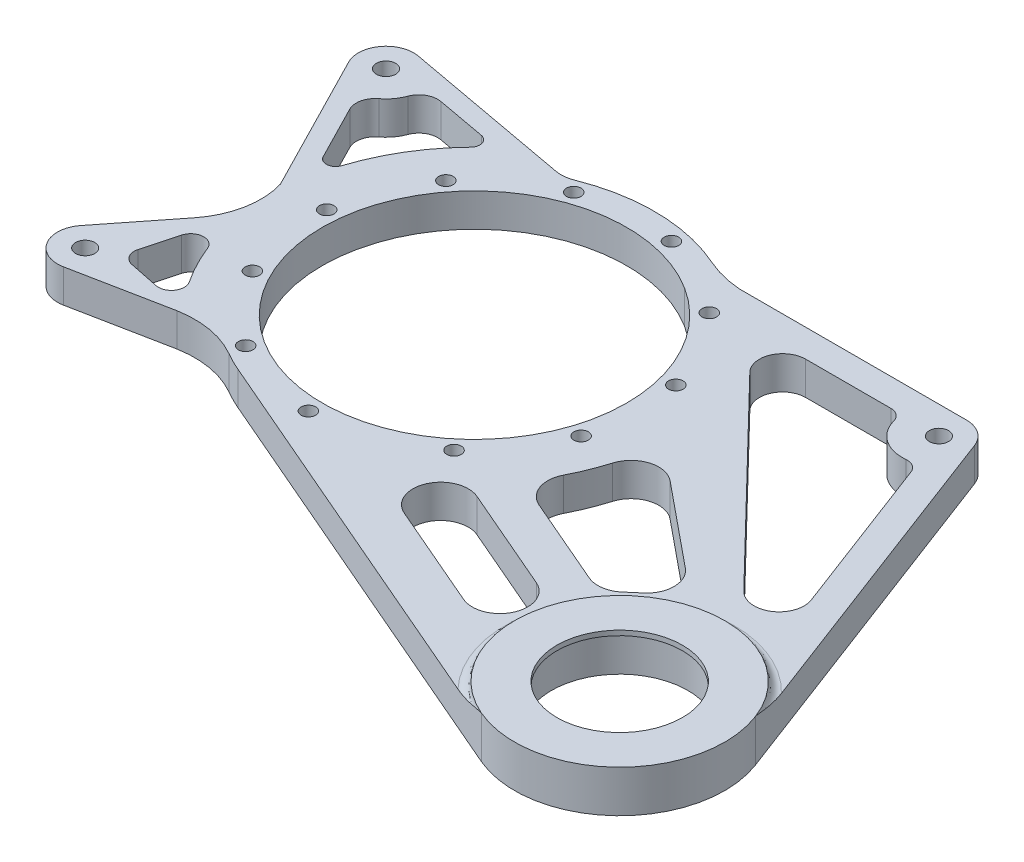
SolidWorks part; units mm, degrees
material "7075-T6 (SN)"
ref_plane "X-Y Datum" through (0, 0, 0) normal (0, 0, 1) x (1, 0, 0)
ref_plane "X-Z Datum" through (0, 0, 0) normal (0, 1, 0) x (1, 0, 0)
ref_plane "Y-Z Datum" through (0, 0, 0) normal (1, 0, 0) x (0, 0, -1)
sketch "Sketch1" plane through (0, 0, 0) normal (0, 1, 0) x (1, 0, 0)
  line L0 (-452.4939, -193.2569) -> (-599.8423, -129.6662)
  line L3 (-568.96, 0) -> (-463.042, 0) construction
  line L4 (-685.8, 0) -> (-568.96, 0) construction
  line L5 (-685.8, -143.2733) -> (-685.8, 0) construction
  line L6 (-685.8, -143.2733) -> (-575.31, -72.8215) construction
  line L7 (-575.31, -72.8215) -> (-438.15, -160.02) construction
  line L8 (-685.8, -1.6598) -> (-575.31, -72.8215) construction
  line L9 (-537.4328, -19.4168) -> (-459.3604, -19.4168)
  line L14 (-652.4813, -91.9261) -> (-669.8039, -113.9002)
  line L15 (-673.1, -130.5733) -> (-698.5, -130.5733) construction
  line L16 (-673.1, -130.5733) -> (-673.1, -155.9733) construction
  line L17 (-673.1, -155.9733) -> (-698.5, -155.9733) construction
  line L18 (-698.5, -130.5733) -> (-698.5, -155.9733) construction
  line L19 (-673.1, -130.5733) -> (-698.5, -155.9733) construction
  line L20 (-673.1, -155.9733) -> (-698.5, -130.5733) construction
  line L21 (-627.8464, -122.6884) -> (-660.4758, -129.1411)
  line L22 (-662.2354, -5.2529) -> (-604.1922, -15.9133)
  line L23 (-672.4346, -18.9616) -> (-647.7651, -67.1526)
  line L25 (-673.1, -12.7) -> (-698.5, -12.7) construction
  line L26 (-673.1, -12.7) -> (-673.1, 12.7) construction
  line L27 (-673.1, 12.7) -> (-698.5, 12.7) construction
  line L28 (-698.5, -12.7) -> (-698.5, 12.7) construction
  line L29 (-673.1, -12.7) -> (-698.5, 12.7) construction
  line L30 (-673.1, 12.7) -> (-698.5, -12.7) construction
  line L32 (-685.8, -130.5733) -> (-673.1, -130.5733) construction
  line L33 (-685.8, -129.1488) -> (-685.8, -130.5733) construction
  line L34 (-668.5282, -112.57) -> (-684.4718, -126.258) construction
  line L35 (-667.4361, -138.3507) -> (-655.5968, -126.5405) construction
  line L36 (-673.1, -139.4633) -> (-670.1269, -139.4633) construction
  line L37 (-673.1, -130.5733) -> (-673.1, -139.4633) construction
  line L38 (-685.8, -130.5733) -> (-673.1, -130.5733) construction
  line L39 (-685.8, -129.1488) -> (-685.8, -130.5733) construction
  line L40 (-668.5282, -112.57) -> (-684.4718, -126.258) construction
  line L41 (-667.4361, -138.3507) -> (-655.5968, -126.5405) construction
  line L42 (-673.1, -139.4633) -> (-670.1269, -139.4633) construction
  line L43 (-673.1, -130.5733) -> (-673.1, -139.4633) construction
  line L44 (-463.042, 0) -> (-463.042, -3.81) construction
  line L45 (-575.31, -72.8215) -> (-459.3604, -28.9418) construction
  line L46 (-450.455, -25.5624) -> (-404.305, -147.1765)
  line L47 (-575.31, -72.8215) -> (-575.31, -78.4445) construction
  line L48 (-655.8976, -11.4734) -> (-668.4375, -1.9195)
  line L49 (-670.3617, -1.27) -> (-673.1, -1.27)
  line L50 (-673.1, -1.27) -> (-673.1, -12.7)
  line L51 (-673.1, -12.7) -> (-684.53, -12.7)
  line L52 (-684.53, -12.7) -> (-684.53, -14.7065)
  line L53 (-682.9809, -17.4336) -> (-666.5478, -27.2313)
  line L56 (-673.1, -1.27) -> (-673.1, -12.7) construction
  line L57 (-673.1, -12.7) -> (-684.53, -12.7) construction
  circle A13 centre (-438.15, -160.02) radius 23.5
  circle A17 centre (-575.31, -72.8215) radius 61.9125 construction
  circle A18 centre (-575.31, -72.8215) radius 52.3875
  circle A29 centre (-438.15, -160.02) radius 36.2 construction
  arc A36 (-588.7133, -12.3772) -> (-550.1347, -16.2586) centre (-575.31, -72.8215) cw
  arc A38 (-627.8464, -122.6884) -> (-606.238, -126.4556) centre (-622.1949, -154.1272) cw
  circle A39 centre (-662.3237, -119.797) radius 3.3
  arc A45 (-684.4718, -126.258) -> (-685.8, -129.1488) centre (-681.99, -129.1488) ccw construction
  circle A46 centre (-662.3237, -119.797) radius 3.3
  circle A47 centre (-662.3237, -119.797) radius 3.3 construction
  arc A48 (-655.5968, -126.5405) -> (-668.5282, -112.57) centre (-662.3237, -119.797) ccw construction
  arc A49 (-670.1269, -139.4633) -> (-667.4361, -138.3507) centre (-670.1269, -135.6533) ccw construction
  arc A50 (-684.4718, -126.258) -> (-685.8, -129.1488) centre (-681.99, -129.1488) ccw construction
  arc A51 (-655.5968, -126.5405) -> (-668.5282, -112.57) centre (-662.3237, -119.797) ccw construction
  arc A52 (-670.1269, -139.4633) -> (-667.4361, -138.3507) centre (-670.1269, -135.6533) ccw construction
  circle A53 centre (-662.3237, -119.797) radius 9.525 construction
  arc A54 (-599.8423, -129.6662) -> (-606.238, -126.4556) centre (-575.31, -72.8215) cw
  arc A55 (-669.8039, -113.9002) -> (-660.4758, -129.1411) centre (-662.3237, -119.797) ccw
  circle A57 centre (-602.253, -5.3549) radius 10.7351 construction
  arc A58 (-588.7133, -12.3772) -> (-598.2717, -15.3244) centre (-575.31, -72.8215) ccw
  arc A59 (-668.4375, -1.9195) -> (-670.3617, -1.27) centre (-670.3617, -4.445) ccw
  arc A60 (-684.53, -14.7065) -> (-682.9809, -17.4336) centre (-681.355, -14.7065) ccw
  arc A61 (-666.5478, -27.2313) -> (-655.8976, -11.4734) centre (-661.67, -19.05) ccw
  arc A65 (-647.7651, -67.1526) -> (-652.4813, -91.9261) centre (-673.9475, -75.0039) cw
  arc A67 (-598.2717, -15.3244) -> (-604.1922, -15.9133) centre (-602.253, -5.3549) cw
  circle A68 centre (-463.042, -3.81) radius 12.7 construction
  circle A69 centre (-459.3604, -28.9418) radius 3.3
  circle A70 centre (-459.3604, -28.9418) radius 9.525 construction
  arc A71 (-550.1347, -16.2586) -> (-537.4328, -19.4168) centre (-534.8559, 18.0692) ccw
  arc A72 (-459.3604, -19.4168) -> (-450.455, -25.5624) centre (-459.3604, -28.9418) cw
  arc A73 (-452.4939, -193.2569) -> (-404.305, -147.1765) centre (-438.15, -160.02) ccw
  circle A74 centre (-685.8, -1.6598) radius 12.7 construction
  circle A75 centre (-663.956, -14.6213) radius 3.3
  circle A76 centre (-663.956, -14.6213) radius 9.525 construction
  arc A77 (-662.2354, -5.2529) -> (-672.4346, -18.9616) centre (-663.956, -14.6213) ccw
  dimension "D7" = 25.4
  dimension "D10" = 123.825
  dimension "D11" = 104.775
  dimension "D12" = 47
  dimension "D13" = 72.4
  dimension "D15" = 26.943
  dimension "D18" = 43.8797
  dimension "D24" = 31.9428
  dimension "D25" = 32.6295
  dimension "D26" = 9.344
  dimension "D29" = 21.9741
  dimension "D33" = 27.3342
  dimension "D34" = 21.844
  dimension "D23" = 19.05
  dimension "D32" = 25.4
  dimension "D38" = 3.81
  dimension "D28" = 21.4701
  dimension "D19" = 37.5744
  dimension "D17" = 25.4
  dimension "D22" = 19.05
  dimension "D1" = 685.8
  dimension "D2" = 116.84
  dimension "D3" = 222.758
  dimension "D5" = 160.02
  dimension "D6" = 117.8733
  dimension "D8" = 72.8215
  dimension "D9" = 110.49
  dimension "D14" = 25.4
  dimension "D16" = 25.1753
  dimension "D20" = 1.6598
  dimension "D21" = 25.4
  dimension "D27" = 247.65
  dimension "D30" = 7.4802
  dimension "D31" = 0
  dimension "D36" = 3.8814
  dimension "D37" = 25.4
  dimension "D43" = 0
extrude "Boss-Extrude1" add sketch "Sketch1" along normal mid plane 11.43
sketch "Sketch2" plane through (0, 5.715, 0) normal (0, 1, 0) x (1, 0, 0)
  circle A1 centre (-438.15, -160.02) radius 23.5 construction
  circle A2 centre (-438.15, -160.02) radius 36.2
  circle A3 centre (-438.15, -160.02) radius 36.2
  circle A4 centre (-438.15, -160.02) radius 23.5
  circle A5 centre (-438.15, -160.02) radius 21.595
  circle M23 centre (-438.15, -160.02) radius 23.5
  dimension "D1" = 12.7
  dimension "D2" = 1.905
extrude "Boss-Extrude2" add sketch "Sketch2" along normal blind 3.0464 contours A3 M23 | A5 M23 region at (-473.3261, 5.715, 160.02) region at (-460.9853, 5.715, 160.02)
fillet "Fillet1" radius 3.175 1 edges at (-463.1685, 5.715, 133.8567)
sketch "Sketch6" plane through (0, 5.715, 0) normal (0, -1, 0) x (1, 0, 0)
  circle A0 centre (-438.15, 160.02) radius 23.5 construction
  circle A1 centre (-438.15, 160.02) radius 21.595
  circle A2 centre (-438.15, 160.02) radius 21.595
  circle A3 centre (-438.15, 160.02) radius 23.5
  dimension "D1" = 0
extrude "Cut-Extrude1" cut sketch "Sketch6" against normal blind 1.392
ref_point "Point1"
ref_point "Point2"
ref_plane "Plane1" through (-438.15, 0.696, 160.02) normal (0.8439, 0, 0.5365) x (0.5365, 0, -0.8439)
ref_plane "Plane2" through (-376.7454, 0, -239.5133) normal (0.8439, 0, 0.5365) x (0.5365, 0, -0.8439)
split line "Split Line1"
split line "Split Line2"
sketch "Sketch8" plane through (0, -5.715, 0) normal (0, -1, 0) x (1, 0, 0)
  circle A0 centre (-575.31, 72.8215) radius 61.9125 construction
  circle A1 centre (-575.31, 72.8215) radius 61.9125
split line "Split Line5"
sketch "Sketch11" plane through (0, -5.715, 0) normal (0, -1, 0) x (1, 0, 0)
  line L0 (-432.5061, 99.7078) -> (-453.4854, 44.4233)
  line L1 (-505.1999, 28.9418) -> (-475.9191, 28.9418)
  line L2 (-446.7225, 108.7412) -> (-510.9243, 42.4554)
  line L6 (-459.3604, 19.4168) -> (-537.4328, 19.4168) construction
  line L8 (-520.863, 126.4041) -> (-484.9521, 141.902)
  line L9 (-507.6372, 118.2797) -> (-477.2622, 131.3885)
  line L10 (-492.3338, 88.4923) -> (-463.6028, 111.9632)
  line L19 (-658.1742, 32.8834) -> (-648.5837, 51.6181)
  line L20 (-644.8026, 14.9109) -> (-627.7247, 18.0475)
  line L21 (-672.4346, 18.9616) -> (-647.7651, 67.1526) construction
  line L22 (-662.2354, 5.2529) -> (-604.1922, 15.9133) construction
  line L23 (-672.4346, 18.9616) -> (-647.7651, 67.1526) construction
  line L24 (-662.2354, 5.2529) -> (-604.1922, 15.9133) construction
  line L25 (-662.3237, 119.797) -> (-575.31, 72.8215) construction
  line L26 (-652.7583, 111.1604) -> (-649.5762, 99.3396)
  line L27 (-649.3552, 116.671) -> (-638.88, 118.8094)
  line L28 (-528.4114, 143.8948) -> (-492.5005, 159.3927)
  line L29 (-599.8423, 129.6662) -> (-452.4939, 193.2569) construction
  line L30 (-404.305, 147.1765) -> (-450.455, 25.5624) construction
  circle A0 centre (-440.5457, 102.7586) radius 8.599 construction
  circle A1 centre (-505.1999, 36.911) radius 7.9692 construction
  circle A2 centre (-475.9191, 33.3868) radius 4.445 construction
  circle A3 centre (-457.6413, 46.0004) radius 4.445 construction
  arc A4 (-475.9191, 28.9418) -> (-471.6261, 32.2344) centre (-475.9191, 33.3868) ccw
  circle A6 centre (-575.31, 72.8215) radius 70.8025
  circle A7 centre (-575.31, 72.8215) radius 70.8025 construction
  circle A9 centre (-459.3604, 28.9418) radius 12.7 construction
  arc A10 (-471.6261, 32.2344) -> (-458.087, 41.5778) centre (-459.3604, 28.9418) cw
  arc A11 (-453.4854, 44.4233) -> (-458.087, 41.5778) centre (-457.6413, 46.0004) cw
  arc A12 (-432.5061, 99.7078) -> (-446.7225, 108.7412) centre (-440.5457, 102.7586) ccw
  arc A13 (-505.1999, 28.9418) -> (-510.9243, 42.4554) centre (-505.1999, 36.911) cw
  circle A14 centre (-524.6372, 135.1494) radius 9.525 construction
  circle A15 centre (-488.7263, 150.6474) radius 9.525 construction
  circle A16 centre (-503.863, 109.5343) radius 9.525 construction
  circle A17 centre (-473.488, 122.6432) radius 9.525 construction
  arc A19 (-512.335, 105.181) -> (-507.4844, 93.1359) centre (-575.31, 72.8215) cw
  circle A20 centre (-498.3598, 95.8688) radius 9.525 construction
  arc A23 (-528.4114, 143.8948) -> (-520.863, 126.4041) centre (-524.6372, 135.1494) ccw
  arc A24 (-492.5005, 159.3927) -> (-484.9521, 141.902) centre (-488.7263, 150.6474) cw
  arc A25 (-507.6372, 118.2797) -> (-512.335, 105.181) centre (-503.863, 109.5343) ccw
  arc A26 (-507.4844, 93.1359) -> (-492.3338, 88.4923) centre (-498.3598, 95.8688) ccw
  circle A28 centre (-469.6288, 119.3397) radius 9.525 construction
  arc A29 (-466.9443, 129.5645) -> (-463.7997, 126.8727) centre (-438.15, 160.02) ccw
  arc A30 (-477.2622, 131.3885) -> (-466.9443, 129.5645) centre (-473.488, 122.6432) cw
  arc A31 (-463.7997, 126.8727) -> (-463.6028, 111.9632) centre (-469.6288, 119.3397) cw
  arc A34 (-468.5527, 188.87) -> (-407.9695, 130.9376) centre (-438.15, 160.02) ccw
  arc A35 (-468.5527, 188.87) -> (-407.9695, 130.9376) centre (-438.15, 160.02) ccw construction
  circle A52 centre (-652.4088, 29.932) radius 6.477 construction
  circle A53 centre (-645.9727, 21.2814) radius 6.477 construction
  circle A54 centre (-645.7462, 50.1656) radius 3.1877 construction
  circle A55 centre (-628.3005, 21.1828) radius 3.1877 construction
  arc A57 (-642.7116, 51.1417) -> (-626.0175, 23.4075) centre (-575.31, 72.8215) ccw
  arc A60 (-642.7116, 51.1417) -> (-648.5837, 51.6181) centre (-645.7462, 50.1656) ccw
  arc A61 (-626.0175, 23.4075) -> (-627.7247, 18.0475) centre (-628.3005, 21.1828) cw
  circle A63 centre (-648.4662, 112.3158) radius 4.445 construction
  circle A64 centre (-637.9909, 114.4542) radius 4.445 construction
  circle A65 centre (-645.284, 100.4951) radius 4.445 construction
  arc A66 (-641.1505, 98.8604) -> (-634.2883, 111.9949) centre (-575.31, 72.8215) cw
  arc A67 (-652.7583, 111.1604) -> (-649.3552, 116.671) centre (-648.4662, 112.3158) cw
  arc A68 (-638.88, 118.8094) -> (-634.2883, 111.9949) centre (-637.9909, 114.4542) cw
  arc A69 (-641.1505, 98.8604) -> (-649.5762, 99.3396) centre (-645.284, 100.4951) cw
  circle A70 centre (-459.3604, 28.9418) radius 3.3 construction
  circle A71 centre (-459.3604, 28.9418) radius 3.3 construction
  arc A74 (-656.3088, 24.7608) -> (-652.0465, 19.0319) centre (-663.956, 14.6213) cw
  circle A75 centre (-663.956, 14.6213) radius 12.7
  circle A76 centre (-663.956, 14.6213) radius 12.7 construction
  arc A77 (-658.1742, 32.8834) -> (-656.3088, 24.7608) centre (-652.4088, 29.932) ccw
  arc A78 (-652.0465, 19.0319) -> (-644.8026, 14.9109) centre (-645.9727, 21.2814) ccw
  dimension "D3" = 8.89
  dimension "D6" = 25.4
  dimension "D10" = 19.05
  dimension "D15" = 12.954
  dimension "D16" = 6.3754
  dimension "D19" = 8.89
  dimension "D4" = 9.525
  dimension "D5" = 9.525
  dimension "D7" = 73.8169
  dimension "D8" = 29.0831
  dimension "D9" = 15.24
  dimension "D11" = 12.7
  dimension "D12" = 14.732
  dimension "D14" = 5.08
  dimension "D17" = 6.35
  dimension "D18" = 6.35
  dimension "D20" = 8.89
  dimension "D21" = 6.858
  dimension "D22" = 15.748
  dimension "D23" = 45.8396
  dimension "D1" = 8.89
  dimension "D13" = 2.54
  dimension "D24" = 3.175
extrude "Cut-Extrude3" cut sketch "Sketch11" against normal through all
sketch "Sketch12" plane through (0, -5.715, 0) normal (0, -1, 0) x (1, 0, 0)
  line L0 (-575.31, 72.8215) -> (-575.31, 159.4351) construction
  line L1 (-685.8, 143.2733) -> (-685.8, 0) construction
  line L2 (-685.8, 143.2733) -> (-685.8, 0)
  arc A0 (-603.416, 117.0312) -> (-547.204, 28.6117) centre (-575.31, 72.8215) ccw construction
  arc A1 (-547.204, 28.6117) -> (-603.416, 117.0312) centre (-575.31, 72.8215) ccw construction
  arc A2 (-603.416, 117.0312) -> (-547.204, 28.6117) centre (-575.31, 72.8215) ccw construction
  arc A3 (-547.204, 28.6117) -> (-603.416, 117.0312) centre (-575.31, 72.8215) ccw construction
  circle A4 centre (-575.31, 129.9715) radius 4.7625 construction
  arc A6 (-550.1347, 16.2586) -> (-599.8423, 129.6662) centre (-575.31, 72.8215) ccw construction
hole_wizard "Ø5.0mm Dowel Hole1" positions "Sketch13" profile "Sketch14" hole size "Ø5.0" standard "ANSI Metric" end condition through all
sketch "Sketch13" plane through (0, -5.715, 0) normal (0, -1, 0) x (-1, 0, 0)
  point P0 (575.31, -129.9715)
sketch "Sketch14" plane through (-575.31, -5.715, 129.9715) normal (1, 0, 0) x (0, 0, -1)
  line L0 (0, 0) -> (0, 15.6702)
  line L1 (0, 15.6702) -> (2.5, 15.6702)
  line L2 (2.5, 15.6702) -> (2.5, 0.025)
  line L3 (2.5, 0.025) -> (2.525, 0)
  line L5 (2.525, 0) -> (0, 0)
  line L6 (-2.5, 0.025) -> (-2.525, 0) construction
  line L11 (0, -6.35) -> (0, 107.95) construction
  dimension "Thru Hole Dia." = 5
  dimension "Thru Hole Depth" = 15.6702
  dimension "Near C'Sink Dia." = 5.05
  dimension "Near C'Sink Angle" = 90
pattern_circular "CirPattern1" count 11 every 32 about axis through (-575.31, 5.715, 72.8215) along (0, -1, 0) of "Ø5.0mm Dowel Hole1"
